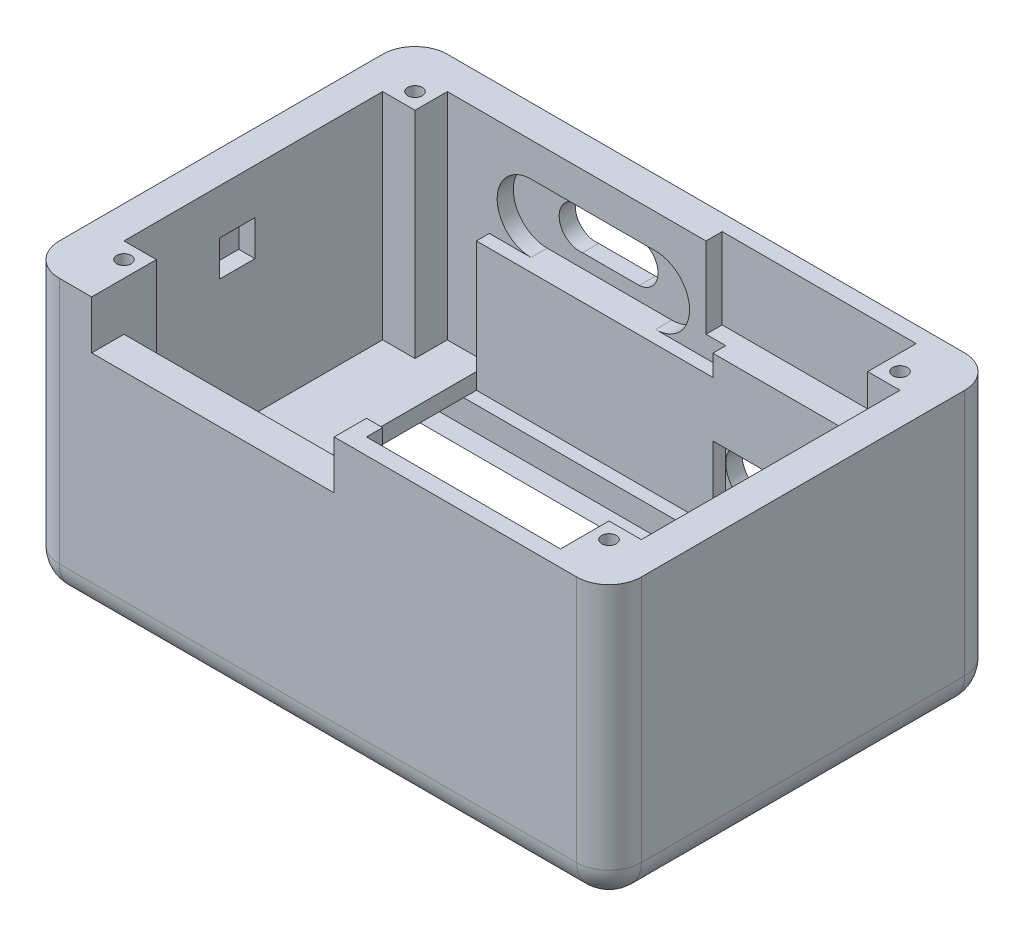
SolidWorks part; units mm, degrees
ref_plane "前视基准面" through (0, 0, 0) normal (0, 0, 1) x (1, 0, 0)
ref_plane "上视基准面" through (0, 0, 0) normal (0, 1, 0) x (1, 0, 0)
ref_plane "右视基准面" through (0, 0, 0) normal (1, 0, 0) x (0, 0, -1)
sketch "草图1" plane through (0, 0, 0) normal (0, 1, 0) x (1, 0, 0)
  line L1 (-72.1576, -30.7504) -> (-36.1576, -30.7504)
  line L2 (-72.1576, -30.7504) -> (-72.1576, -6.7504)
  line L3 (-72.1576, -6.7504) -> (-36.1576, -6.7504)
  line L4 (-36.1576, -30.7504) -> (-36.1576, -6.7504)
  dimension "D1" = 24
  dimension "D2" = 36
extrude "凸台-拉伸1" add sketch "草图1" along normal blind 17.3 contours L2 L1 L4 L3
sketch "草图2" plane through (0, 17.3, 0) normal (0, 1, 0) x (1, 0, 0)
  line L0 (-36.1576, -30.7504) -> (-36.1576, -6.7504) construction
  line L1 (-70.1576, -8.7504) -> (-38.1576, -8.7504)
  line L2 (-70.1576, -8.7504) -> (-70.1576, -28.7504)
  line L3 (-70.1576, -28.7504) -> (-38.1576, -28.7504)
  line L4 (-38.1576, -8.7504) -> (-38.1576, -28.7504)
  line L5 (-72.1576, -30.7504) -> (-36.1576, -30.7504) construction
  line L6 (-72.1576, -30.7504) -> (-72.1576, -6.7504) construction
  line L7 (-72.1576, -6.7504) -> (-36.1576, -6.7504) construction
  dimension "D1" = 2
  dimension "D2" = 2
  dimension "D3" = 2
  dimension "D4" = 2
extrude "切除-拉伸1" cut sketch "草图2" against normal blind 14.3
sketch "草图4" plane through (0, 0, 0) normal (0, -1, 0) x (-1, 0, 0)
  line L0 (72.1576, -30.7504) -> (72.1576, -6.7504) construction
  line L1 (68.9576, -11.5404) -> (53.7476, -11.5404)
  line L2 (68.9576, -11.5404) -> (68.9576, -26.7504)
  line L3 (68.9576, -26.7504) -> (53.7476, -26.7504)
  line L4 (53.7476, -11.5404) -> (53.7476, -26.7504)
  line L6 (72.1576, -30.7504) -> (36.1576, -30.7504) construction
  dimension "D1" = 15.21
  dimension "D2" = 15.21
  dimension "D3" = 3.2
  dimension "D4" = 4
extrude "切除-拉伸2" cut sketch "草图4" against normal blind 15 contours L2 L1 L4 L3
sketch "草图6" plane through (0, 0, 30.7504) normal (0, 0, 1) x (1, 0, 0)
  line L1 (-53.1576, 14.3) -> (-68.1576, 14.3)
  line L2 (-53.1576, 14.3) -> (-53.1576, 17.3)
  line L3 (-53.1576, 17.3) -> (-68.1576, 17.3)
  line L4 (-68.1576, 14.3) -> (-68.1576, 17.3)
  line L5 (-72.1576, 17.3) -> (-72.1576, 0) construction
  line L6 (-72.1576, 17.3) -> (-36.1576, 17.3) construction
  point P9 (-68.1576, 15.8)
  dimension "D2" = 3
  dimension "D3" = 4
  dimension "D4" = 15
extrude "切除-拉伸4" cut sketch "草图6" against normal blind 5
sketch "草图7" plane through (0, 0, 6.7504) normal (0, 0, -1) x (-1, 0, 0)
  line L0 (72.1576, 0) -> (36.1576, 0) construction
  line L3 (49.3376, 6) -> (43.1376, 6) construction
  line L4 (49.3376, 2.4) -> (43.1376, 2.4)
  line L5 (49.3376, 9.6) -> (43.1376, 9.6)
  line L6 (36.1576, 17.3) -> (36.1576, 0) construction
  arc A2 (49.3376, 2.4) -> (49.3376, 9.6) centre (49.3376, 6) ccw
  arc A3 (43.1376, 9.6) -> (43.1376, 2.4) centre (43.1376, 6) ccw
  point P2 (39.5376, 6)
  point P10 (46.2376, 6)
  point P15 (46.2376, 9.6)
  dimension "D1" = 2.4
  dimension "D2" = 3.38
  dimension "D3" = 6.2
  dimension "D4" = 7.2
extrude "切除-拉伸7" cut sketch "草图7" against normal blind 1
sketch "草图9" plane through (0, 0, 7.7504) normal (0, 0, -1) x (-1, 0, 0)
  line L0 (49.3376, 6) -> (43.5376, 6) construction
  line L1 (49.3376, 4.4) -> (43.5376, 4.4)
  line L2 (49.3376, 7.6) -> (43.5376, 7.6)
  line L3 (49.3376, 9.6) -> (43.1376, 9.6) construction
  arc A0 (49.3376, 4.4) -> (49.3376, 7.6) centre (49.3376, 6) ccw
  arc A1 (43.5376, 7.6) -> (43.5376, 4.4) centre (43.5376, 6) ccw
  arc A2 (49.3376, 2.4) -> (49.3376, 9.6) centre (49.3376, 6) ccw construction
  point P2 (46.4376, 6)
  point P12 (52.9376, 6)
  point P13 (50.9376, 6)
  point P14 (41.9376, 6)
  dimension "D1" = 2
  dimension "D2" = 2
  dimension "D3" = 3.2
  dimension "D4" = 9
extrude "切除-拉伸8" cut sketch "草图9" against normal blind 1
sketch "草图11" plane through (0, 3, 0) normal (0, 1, 0) x (1, 0, 0)
  line L0 (-68.9576, -26.7504) -> (-68.9576, -11.5404) construction
  line L1 (-39.6576, -10.3404) -> (-70.1576, -10.3404)
  line L2 (-39.6576, -10.3404) -> (-39.6576, -27.9404)
  line L3 (-39.6576, -27.9404) -> (-70.1576, -27.9404)
  line L4 (-70.1576, -10.3404) -> (-70.1576, -27.9404)
  line L5 (-53.7476, -11.5404) -> (-68.9576, -11.5404) construction
  line L7 (-38.1576, -28.7504) -> (-38.1576, -8.7504) construction
  dimension "D1" = 1.5
  dimension "D2" = 17.6
  dimension "D3" = 1.2
  dimension "D4" = 1.2
extrude "切除-拉伸10" cut sketch "草图11" against normal blind 1.5
sketch "草图13" plane through (0, 17.3, 0) normal (0, 1, 0) x (1, 0, 0)
  line L5 (-38.1576, -28.7504) -> (-38.1576, -8.7504) construction
  line L6 (-53.1576, -28.7504) -> (-38.1576, -28.7504) construction
  line L7 (-52.1576, -28.7504) -> (-40.1576, -28.7504)
  line L8 (-52.1576, -28.7504) -> (-52.1576, -29.7504)
  line L9 (-52.1576, -29.7504) -> (-40.1576, -29.7504)
  line L10 (-40.1576, -28.7504) -> (-40.1576, -29.7504)
  line L11 (-38.1576, -8.7504) -> (-70.1576, -8.7504) construction
  line L12 (-52.1576, -8.7504) -> (-40.1576, -8.7504)
  line L13 (-52.1576, -8.7504) -> (-52.1576, -7.7504)
  line L14 (-52.1576, -7.7504) -> (-40.1576, -7.7504)
  line L15 (-40.1576, -8.7504) -> (-40.1576, -7.7504)
  dimension "D1" = 1
  dimension "D2" = 1
  dimension "D3" = 12
  dimension "D4" = 2
extrude "切除-拉伸12" cut sketch "草图13" against normal blind 5
fillet "圆角2" radius 2 8 edges at (-36.1576, 8.65, 6.7504) (-54.1576, 0, 6.7504) (-54.1576, 0, 30.7504) (-72.1576, 0, 18.7504) (-72.1576, 8.65, 30.7504) (-36.1576, 8.65, 30.7504) (-36.1576, 0, 18.7504) (-72.1576, 8.65, 6.7504)
sketch "草图15" plane through (0, 3, 0) normal (0, 1, 0) x (1, 0, 0)
  line L0 (-38.1576, -8.7504) -> (-70.1576, -8.7504) construction
  line L1 (-65.5576, -9.5504) -> (-50.9376, -9.5504)
  line L2 (-65.5576, -9.5504) -> (-65.5576, -8.7504)
  line L3 (-65.5576, -8.7504) -> (-50.9376, -8.7504)
  line L4 (-50.9376, -9.5504) -> (-50.9376, -8.7504)
  line L7 (-70.1576, -8.7504) -> (-70.1576, -10.3404) construction
  point P8 (-70.1576, -9.5454)
  dimension "D1" = 0.8
  dimension "D2" = 4.6
extrude "凸台-拉伸2" add sketch "草图15" along normal blind 8
chamfer "倒角2" distance 1.5 distance2 1.5 4 edges at (-61.3526, 0, 26.7504) (-53.7476, 0, 19.1454) (-61.3526, 0, 11.5404) (-68.9576, 0, 19.1454)
sketch "草图19" plane through (-70.1576, 0, 0) normal (1, 0, 0) x (0, 0, -1)
  line L0 (-8.7504, 17.3) -> (-28.7504, 17.3) construction
  line L1 (-20.8504, 14.5) -> (-18.6504, 14.5)
  line L2 (-20.8504, 14.5) -> (-20.8504, 12.3)
  line L3 (-20.8504, 12.3) -> (-18.6504, 12.3)
  line L4 (-18.6504, 14.5) -> (-18.6504, 12.3)
  line L5 (-30.7504, 17.3) -> (-30.7504, 14.3) construction
  dimension "D1" = 2.2
  dimension "D2" = 2.2
  dimension "D3" = 2.8
  dimension "D4" = 9.9
extrude "切除-拉伸16" cut sketch "草图19" against normal blind 1
sketch "草图21" plane through (-38.1576, 0, 0) normal (-1, 0, 0) x (0, 0, 1)
  line L0 (28.7504, 3) -> (8.7504, 3) construction
  line L1 (12.5504, 4) -> (8.7504, 4)
  line L2 (12.5504, 4) -> (12.5504, 3)
  line L3 (12.5504, 3) -> (8.7504, 3)
  line L4 (8.7504, 4) -> (8.7504, 3)
  line L6 (28.7504, 3) -> (25.7504, 3)
  line L7 (28.7504, 3) -> (28.7504, 4)
  line L8 (28.7504, 4) -> (25.7504, 4)
  line L9 (25.7504, 3) -> (25.7504, 4)
  dimension "D1" = 3.8
  dimension "D2" = 3
  dimension "D3" = 1
extrude "凸台-拉伸4" add sketch "草图21" along normal blind 3
fillet "圆角8" radius 1 1 edges at (-39.6576, 3, 19.1504) type face fillet first side face at (-39.6576, 2.5, 19.1438) second side face at (-38.9076, 3, 19.1504)
sketch "草图24" plane through (-38.1576, 0, 0) normal (-1, 0, 0) x (0, 0, 1)
  line L0 (25.7504, 3) -> (12.5504, 3) construction
  line L1 (25.7504, 3) -> (12.5504, 3)
  line L2 (25.7504, 3) -> (25.7504, 12.5)
  line L3 (25.7504, 12.5) -> (12.5504, 12.5)
  line L4 (12.5504, 3) -> (12.5504, 12.5)
  line L5 (25.7504, 4) -> (25.7504, 3) construction
  line L6 (12.5504, 3) -> (12.5504, 4) construction
  dimension "D1" = 9.5
extrude "切除-拉伸17" cut sketch "草图24" against normal blind 1
sketch "草图27" plane through (0, 0, 8.7504) normal (0, 0, 1) x (1, 0, 0)
  line L0 (-65.5576, 11) -> (-65.5576, 3) construction
  line L1 (-70.1576, 3) -> (-65.5576, 3)
  line L2 (-70.1576, 3) -> (-70.1576, 4)
  line L3 (-70.1576, 4) -> (-65.5576, 4)
  line L4 (-65.5576, 3) -> (-65.5576, 4)
  dimension "D1" = 1
extrude "凸台-拉伸6" add sketch "草图27" along normal up to next
sketch "草图28" plane through (0, 4, 0) normal (0, 1, 0) x (1, 0, 0)
  line L1 (-70.1576, -8.7504) -> (-68.1576, -8.7504)
  line L2 (-70.1576, -8.7504) -> (-70.1576, -10.7504)
  line L3 (-70.1576, -10.7504) -> (-68.1576, -10.7504)
  line L4 (-68.1576, -8.7504) -> (-68.1576, -10.7504)
  line L5 (-38.1576, -8.7504) -> (-40.1576, -8.7504)
  line L6 (-38.1576, -8.7504) -> (-38.1576, -10.7504)
  line L7 (-38.1576, -10.7504) -> (-40.1576, -10.7504)
  line L8 (-40.1576, -8.7504) -> (-40.1576, -10.7504)
  line L9 (-70.1576, -28.7504) -> (-68.1576, -28.7504)
  line L10 (-70.1576, -28.7504) -> (-70.1576, -26.7504)
  line L11 (-70.1576, -26.7504) -> (-68.1576, -26.7504)
  line L12 (-68.1576, -28.7504) -> (-68.1576, -26.7504)
  line L13 (-38.1576, -28.7504) -> (-40.1576, -28.7504)
  line L14 (-38.1576, -28.7504) -> (-38.1576, -26.7504)
  line L15 (-38.1576, -26.7504) -> (-40.1576, -26.7504)
  line L16 (-40.1576, -28.7504) -> (-40.1576, -26.7504)
  dimension "D1" = 2
extrude "凸台-拉伸7" add sketch "草图28" along normal up to surface (13.3 mm away) up to face at (-52.5742, 17.3, 20.5838)
sketch "草图29" plane through (0, 17.3, 0) normal (0, 1, 0) x (1, 0, 0)
  line L1 (-68.1576, -30.7504) -> (-68.1576, -26.7504) construction
  line L2 (-70.1576, -10.7504) -> (-68.1576, -10.7504) construction
  line L3 (-40.1576, -7.7504) -> (-40.1576, -10.7504) construction
  line L5 (-70.1576, -30.7504) -> (-68.1576, -30.7504) construction
  circle A0 centre (-69.1576, -9.7504) radius 0.45
  circle A1 centre (-69.1576, -27.7504) radius 0.45
  circle A2 centre (-39.1576, -9.7504) radius 0.45
  circle A3 centre (-39.1576, -27.7504) radius 0.45
  dimension "D1" = 0.9
  dimension "D2" = 3
  dimension "D3" = 1
  dimension "D4" = 1
  dimension "D5" = 1
extrude "切除-拉伸18" cut sketch "草图29" against normal blind 6
sketch "草图31" plane through (0, 0, 8.7504) normal (0, 0, 1) x (1, 0, 0)
  line L1 (-50.9376, 7.6) -> (-40.1576, 7.6)
  line L2 (-50.9376, 7.6) -> (-50.9376, 12.3)
  line L3 (-50.9376, 12.3) -> (-40.1576, 12.3)
  line L4 (-40.1576, 7.6) -> (-40.1576, 12.3)
  line L5 (-52.1576, 12.3) -> (-40.1576, 12.3) construction
  line L6 (-50.9376, 11) -> (-50.9376, 6) construction
  line L7 (-40.1576, 12.3) -> (-40.1576, 4) construction
  line L8 (-49.3376, 7.6) -> (-43.5376, 7.6) construction
extrude "凸台-拉伸8" add sketch "草图31" along normal blind 0.8
sketch "草图32" plane through (0, 0, 8.7504) normal (0, 0, 1) x (1, 0, 0)
  line L0 (-55.2765, 13.1) -> (-62.9765, 13.1) construction
  line L1 (-55.2765, 11) -> (-62.9765, 11)
  line L2 (-55.2765, 15.2) -> (-62.9765, 15.2)
  line L3 (-50.9376, 11) -> (-65.5576, 11) construction
  arc A0 (-55.2765, 11) -> (-55.2765, 15.2) centre (-55.2765, 13.1) ccw
  arc A1 (-62.9765, 15.2) -> (-62.9765, 11) centre (-62.9765, 13.1) ccw
  point P2 (-59.1265, 13.1)
  dimension "D1" = 7.7
  dimension "D2" = 4.2
extrude "切除-拉伸19" cut sketch "草图32" against normal blind 1 contours L1 A1 L2 A0
sketch "草图33" plane through (0, 0, 7.7504) normal (0, 0, 1) x (1, 0, 0)
  line L0 (-60.7872, 14.35) -> (-57.2872, 14.35)
  line L1 (-57.2872, 11.85) -> (-60.7872, 11.85)
  line L6 (-55.2765, 15.2) -> (-62.9765, 15.2) construction
  arc A0 (-57.2872, 11.85) -> (-57.2872, 14.35) centre (-57.3765, 13.1) ccw
  arc A1 (-60.7872, 14.35) -> (-60.7872, 11.85) centre (-60.9765, 13.1) ccw
  arc A3 (-62.9765, 15.2) -> (-62.9765, 11) centre (-62.9765, 13.1) ccw construction
  point P9 (0, 0)
  dimension "D2" = 3.6
  dimension "D1" = 2.5
  dimension "D3" = 2
  dimension "D4" = 0.85
extrude "切除-拉伸20" cut sketch "草图33" against normal up to next
